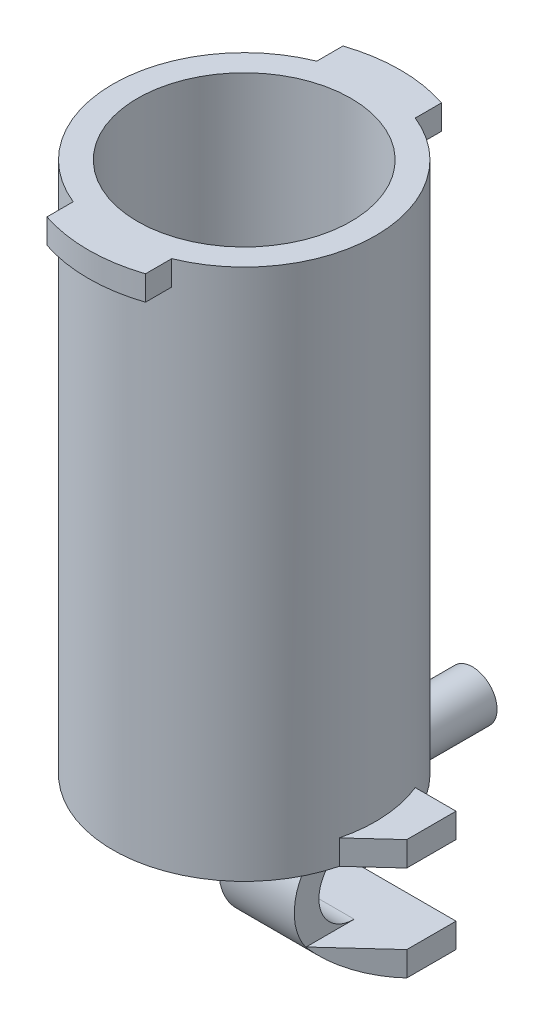
SolidWorks part; units mm, degrees
ref_plane "Front Plane" through (0, 0, 0) normal (0, 0, 1) x (1, 0, 0)
ref_plane "Top Plane" through (0, 0, 0) normal (0, 1, 0) x (1, 0, 0)
ref_plane "Right Plane" through (0, 0, 0) normal (1, 0, 0) x (0, 0, -1)
sketch "Sketch1" plane through (0, 0, 0) normal (0, 1, 0) x (1, 0, 0)
  circle A0 centre (0, 0) radius 8
extrude "Boss-Extrude1" add sketch "Sketch1" along normal blind 32.4
shell "Shell1" thickness 1.5 removed face at (0, 32.4, 8)
sketch "Sketch2" plane through (0, 0, 0) normal (0, -1, 0) x (1, 0, 0)
  circle A2 centre (0, -3) radius 3.5
extrude "Boss-Extrude2" add sketch "Sketch2" along normal blind 5.3
sketch "Sketch3" plane through (0, 0, 0) normal (1, 0, 0) x (0, 0, -1)
  line L0 (0, 4.9697) -> (0, 0) construction
  line L1 (0, 1.5) -> (0, 0)
  line L2 (0, -4.3) -> (0, -5.8)
  line L3 (0, -4.3) -> (0, -6.6365) construction
  arc A0 (0, 0) -> (0, -4.3) centre (0, -2.15) ccw
  arc A1 (0, 1.5) -> (0, -5.8) centre (0, -2.15) ccw
extrude "Boss-Extrude3" add sketch "Sketch3" along normal blind 6.7 contours A1 L2 A0 L1
sketch "Sketch4" plane through (0, -5.3, 0) normal (0, -1, 0) x (1, 0, 0)
  line L0 (0, 0) -> (2.1, 0)
  line L1 (6.7, 0) -> (0, 0) construction
  line L2 (2.1, 0) -> (2.1, 5.477)
  line L3 (2.1, 5.477) -> (0, 5.477)
  line L4 (0, 5.477) -> (0, 0)
extrude "Cut-Extrude1" cut sketch "Sketch4" along normal blind 9
sketch "Sketch5" plane through (0, 0, 0) normal (0, -1, 0) x (1, 0, 0)
  line L0 (0, 0.5) -> (0, 3.65)
  line L1 (0, 3.65) -> (0, 1.8439) construction
  line L2 (2.1, -0.2) -> (2.1, 3.65)
  line L3 (6.7, 3.65) -> (0, 3.65) construction
  line L4 (2.1, 3.65) -> (0, 3.65)
  arc A0 (2.1, -0.2) -> (0, 0.5) centre (0, -3) ccw
extrude "Cut-Extrude2" cut sketch "Sketch5" along normal blind 9
sketch "Sketch6" plane through (0, -5.3, 0) normal (0, -1, 0) x (1, 0, 0)
  line L0 (-1.4347, -3) -> (2.2984, -3) construction
ref_plane "Plane1" through (0, 0, -3) normal (0, 0, 1) x (1, 0, 0)
sketch "Sketch8" plane through (0, 0, -3) normal (0, 0, 1) x (1, 0, 0)
  line L0 (0, 0) -> (0, -7.6173) construction
  circle A1 centre (0, -2.7845) radius 2.45
extrude "Boss-Extrude4" add sketch "Sketch8" against normal blind 4.8
sketch "Sketch9" plane through (0, 0, -7.8) normal (0, 0, -1) x (-1, 0, 0)
  circle A0 centre (0, -2.7845) radius 1.5
extrude "Boss-Extrude5" add sketch "Sketch9" along normal blind 6.1
sketch "Sketch10" plane through (0, 0, -13.9) normal (0, 0, -1) x (-1, 0, 0)
  circle A0 centre (0, -2.7845) radius 0.75
extrude "Cut-Extrude3" cut sketch "Sketch10" against normal blind 10.1
sketch "Sketch11" plane through (0, -5.3, 0) normal (0, -1, 0) x (1, 0, 0)
  circle A1 centre (0, -3) radius 2
extrude "Cut-Extrude4" cut sketch "Sketch11" against normal through all
sketch "Sketch12" plane through (0, -5.3, 0) normal (0, -1, 0) x (1, 0, 0)
  circle A0 centre (0, -3) radius 2
extrude "Boss-Extrude6" add sketch "Sketch12" against normal blind 1.5 separate body
sketch "Sketch16" plane through (6.7, 0, 0) normal (1, 0, 0) x (0, 0, -1)
  line L0 (0, -4.3) -> (0, -5.8)
  line L1 (0, -4.3) -> (3, -4.3)
  line L2 (0, -5.8) -> (3, -5.8)
  line L3 (3, -4.3) -> (3, -5.8)
  line L4 (0, -4.3) -> (0, -5.8) construction
  line L5 (-2.15, -2.15) -> (-4.1057, -2.15) construction
  line L6 (0, 1.5) -> (3, 1.5)
  line L7 (3, 0) -> (3, 1.5)
  line L8 (0, 0) -> (3, 0)
  line L9 (0, 0) -> (0, 1.5)
  arc A0 (0, 0) -> (0, -4.3) centre (0, -2.15) ccw construction
extrude "Boss-Extrude9" add sketch "Sketch16" along normal blind 3.2 and the other way up to surface (4.6 mm away) other way up to face at (2.1, -2.7511, 1.7196)
sketch "Sketch17" plane through (0, -4.3, 0) normal (0, 1, 0) x (1, 0, 0)
  line L0 (6.7, 0) -> (6.7, -2.9284)
  line L5 (6.7, -2.9284) -> (9.9, 0)
  line L6 (9.9, 3) -> (9.9, 0) construction
  line L7 (9.9, 0) -> (6.7, 0)
extrude "Boss-Extrude10" add sketch "Sketch17" against normal up to surface (1.5 mm away) contours L0 L5 L7 up to face at (6.14, -5.8, -1.2)
sketch "Sketch18" plane through (6.7, 0, 0) normal (-1, 0, 0) x (0, 0, 1)
  line L0 (2.9284, -5.8) -> (2.9284, -4.3288)
  line L1 (2.9284, -5.8) -> (0, -5.8)
  arc A0 (0, -5.8) -> (2.9284, -4.3288) centre (0, -2.15) ccw
extrude "Cut-Extrude5" cut sketch "Sketch18" against normal through all
sketch "Sketch19" plane through (0, -4.3, 0) normal (0, 1, 0) x (1, 0, 0)
  line L0 (9.9, 0) -> (6.7, -2.9284)
  line L5 (6.7, 0) -> (6.7, -2.9284)
  line L6 (9.9, 0) -> (6.7, 0)
extrude "Boss-Extrude11" add sketch "Sketch19" along normal up to surface (5.8 mm away) contours L0 L5 L6 up to face at (8.8402, 1.5, -1.507)
sketch "Sketch20" plane through (0, 0, 0) normal (0, 0, -1) x (-1, 0, 0)
  line L0 (-3.5, -4.3) -> (-9.9, -4.3) construction
  line L1 (-9.9, 0) -> (-6.7, 0)
  line L2 (-9.9, 0) -> (-9.9, -4.3)
  line L3 (-9.9, -4.3) -> (-6.7, -4.3)
  line L4 (-6.7, 0) -> (-6.7, -4.3)
extrude "Cut-Extrude6" cut sketch "Sketch20" against normal through all
sketch "Sketch21" plane through (2.1, 0, 0) normal (-1, 0, 0) x (0, 0, 1)
  circle A0 centre (0, -2.15) radius 2.15
extrude "Boss-Extrude12" add sketch "Sketch21" against normal blind 0.001
mirror "Mirror1" about plane through (0, 0, 0) normal (1, 0, 0) of bodies 119
sketch "Sketch22" plane through (0, 32.4, 0) normal (0, 1, 0) x (1, 0, 0)
  line L2 (3, 7.4162) -> (3, 9.0139)
  line L4 (-3, 7.4162) -> (-3, 9.0139)
  line L5 (3, -7.4162) -> (3, -9.0139)
  line L6 (-3, -7.4162) -> (-3, -9.0139)
  arc A0 (3, 9.0139) -> (-3, 9.0139) centre (0, 0) ccw
  arc A1 (3, 7.4162) -> (-3, 7.4162) centre (0, 0) ccw
  arc A2 (3, -7.4162) -> (-3, -7.4162) centre (0, 0) cw
  arc A3 (3, -9.0139) -> (-3, -9.0139) centre (0, 0) cw
extrude "Boss-Extrude13" add sketch "Sketch22" against normal blind 1.5
